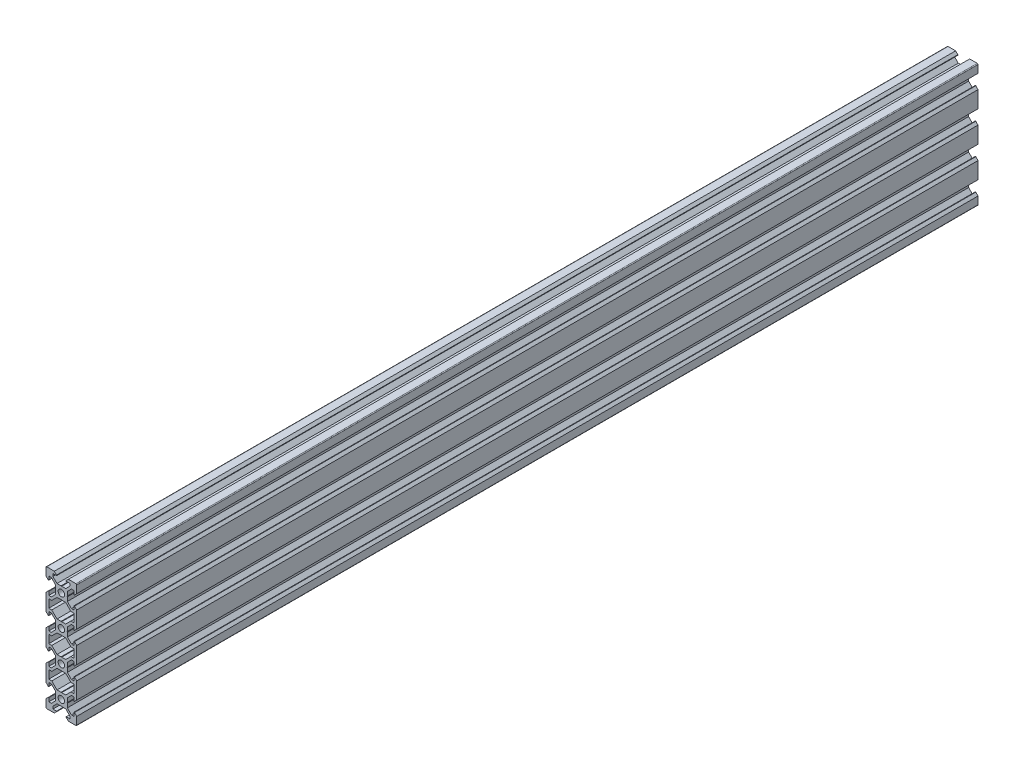
SolidWorks part; units mm, degrees
ref_plane "Plan de face" through (0, 0, 0) normal (0, 0, 1) x (1, 0, 0)
ref_plane "Plan de dessus" through (0, 0, 0) normal (0, 1, 0) x (1, 0, 0)
ref_plane "Plan de droite" through (0, 0, 0) normal (1, 0, 0) x (0, 0, -1)
ref_axis "Axe" through (0, 0, -13.782) along (0, 0, 1)
sketch "Esquisse1" plane through (0, 0, 0) normal (0, 0, 1) x (1, 0, 0)
  line L0 (0, 27.6392) -> (0, -27.6392) construction
  line L1 (-33.6074, 0) -> (33.6074, 0) construction
  line L2 (0, 0) -> (-22.2114, 22.2114) construction
  line L3 (-9.5, 10) -> (-4.58, 10)
  line L4 (-4.58, 10) -> (-3.125, 8.545)
  line L5 (-3.125, 8.545) -> (-3.125, 8.2)
  line L6 (-3.125, 8.2) -> (-5.5, 8.2)
  line L7 (-2.8393, 3.9) -> (-5.5, 6.5607)
  line L8 (-2.8393, 3.9) -> (-0.21, 3.9)
  line L9 (-5.5, 6.5607) -> (-5.5, 8.2)
  line L10 (0, 3.69) -> (0, 2.1)
  line L11 (-3.9, 2.8393) -> (-6.5607, 5.5)
  line L12 (-8.545, 3.125) -> (-8.2, 3.125)
  line L13 (-8.2, 3.125) -> (-8.2, 5.5)
  line L14 (-6.5607, 5.5) -> (-8.2, 5.5)
  line L15 (-10, 4.58) -> (-8.545, 3.125)
  line L16 (-10, 9.5) -> (-10, 4.58)
  line L17 (-0.21, 3.9) -> (0, 3.69)
  line L18 (-3.9, 2.8393) -> (-3.9, 0.21)
  line L19 (-6.2393, -12.7) -> (-8.2, -12.7)
  line L20 (-3.9, 0.21) -> (-3.69, 0)
  line L21 (-0.21, -3.9) -> (0, -3.69)
  line L22 (0, -3.69) -> (0, -2.1)
  line L23 (-6.5607, -5.5) -> (-8.2, -5.5)
  line L24 (-2.8393, -3.9) -> (-0.21, -3.9)
  line L25 (-8.545, -3.125) -> (-8.2, -3.125)
  line L26 (-10, -4.58) -> (-8.545, -3.125)
  line L27 (-8.2, -3.125) -> (-8.2, -5.5)
  line L28 (-2.8393, -3.9) -> (-6.2393, -7.3)
  line L29 (-3.9, -2.8393) -> (-6.5607, -5.5)
  line L30 (-3.9, -2.8393) -> (-3.9, -0.21)
  line L31 (-3.9, -0.21) -> (-3.69, 0)
  line L32 (-6.2393, -7.3) -> (-8.2, -7.3)
  line L33 (-8.2, -7.3) -> (-8.2, -12.7)
  line L34 (-8.2, -10) -> (-10, -10) construction
  line L35 (-10, -15.42) -> (-10, -4.58)
  line L36 (-3.9, -19.79) -> (-3.69, -20)
  line L37 (-3.9, -17.1607) -> (-3.9, -19.79)
  line L38 (-3.9, -17.1607) -> (-6.5607, -14.5)
  line L39 (-2.8393, -16.1) -> (-6.2393, -12.7)
  line L40 (-8.2, -16.875) -> (-8.2, -14.5)
  line L41 (-10, -15.42) -> (-8.545, -16.875)
  line L42 (-8.545, -16.875) -> (-8.2, -16.875)
  line L43 (-2.8393, -16.1) -> (-0.21, -16.1)
  line L44 (-6.5607, -14.5) -> (-8.2, -14.5)
  line L45 (0, -16.31) -> (0, -17.9)
  line L46 (-0.21, -16.1) -> (0, -16.31)
  line L47 (-8.2, -30) -> (-10, -30) construction
  line L48 (-3.69, -20) -> (0, -20) construction
  line L49 (-0.21, -23.9) -> (0, -23.69)
  line L50 (0, -23.69) -> (0, -22.1)
  line L51 (-6.5607, -25.5) -> (-8.2, -25.5)
  line L52 (-2.8393, -23.9) -> (-0.21, -23.9)
  line L53 (-8.545, -23.125) -> (-8.2, -23.125)
  line L54 (-10, -24.58) -> (-8.545, -23.125)
  line L55 (-8.2, -23.125) -> (-8.2, -25.5)
  line L56 (-2.8393, -23.9) -> (-6.2393, -27.3)
  line L57 (-3.9, -22.8393) -> (-6.5607, -25.5)
  line L58 (-3.9, -22.8393) -> (-3.9, -20.21)
  line L59 (-3.9, -20.21) -> (-3.69, -20)
  line L60 (-10, -24.58) -> (-10, -35.42)
  line L61 (-8.2, -32.7) -> (-8.2, -27.3)
  line L62 (-3.69, -40) -> (0, -40) construction
  line L63 (-8.2, -50) -> (-10, -50) construction
  line L64 (0, -60) -> (-22.2114, -82.2114) construction
  line L65 (-33.6074, -60) -> (33.6074, -60) construction
  line L66 (0, -87.6392) -> (0, -32.3608) construction
  line L67 (-6.2393, -32.7) -> (-8.2, -32.7)
  line L68 (-3.9, -39.79) -> (-3.69, -40)
  line L69 (-3.9, -37.1607) -> (-3.9, -39.79)
  line L70 (-3.9, -37.1607) -> (-6.5607, -34.5)
  line L71 (-2.8393, -36.1) -> (-6.2393, -32.7)
  line L72 (-8.2, -36.875) -> (-8.2, -34.5)
  line L73 (-10, -35.42) -> (-8.545, -36.875)
  line L74 (-8.545, -36.875) -> (-8.2, -36.875)
  line L75 (-6.2393, -27.3) -> (-8.2, -27.3)
  line L76 (-2.8393, -36.1) -> (-0.21, -36.1)
  line L77 (-6.5607, -34.5) -> (-8.2, -34.5)
  line L78 (0, -36.31) -> (0, -37.9)
  line L79 (-0.21, -36.1) -> (0, -36.31)
  line L80 (-0.21, -43.9) -> (0, -43.69)
  line L81 (0, -43.69) -> (0, -42.1)
  line L82 (-6.5607, -45.5) -> (-8.2, -45.5)
  line L83 (-2.8393, -43.9) -> (-0.21, -43.9)
  line L84 (-8.545, -43.125) -> (-8.2, -43.125)
  line L85 (-10, -44.58) -> (-8.545, -43.125)
  line L86 (-8.2, -43.125) -> (-8.2, -45.5)
  line L87 (-2.8393, -43.9) -> (-6.2393, -47.3)
  line L88 (-3.9, -42.8393) -> (-6.5607, -45.5)
  line L89 (-3.9, -42.8393) -> (-3.9, -40.21)
  line L90 (-3.9, -40.21) -> (-3.69, -40)
  line L91 (-10, -44.58) -> (-10, -55.42)
  line L92 (-8.2, -52.7) -> (-8.2, -47.3)
  line L93 (-6.2393, -52.7) -> (-8.2, -52.7)
  line L94 (-3.9, -59.79) -> (-3.69, -60)
  line L95 (-3.9, -57.1607) -> (-3.9, -59.79)
  line L96 (-3.9, -57.1607) -> (-6.5607, -54.5)
  line L97 (-2.8393, -56.1) -> (-6.2393, -52.7)
  line L98 (-8.2, -56.875) -> (-8.2, -54.5)
  line L99 (-10, -55.42) -> (-8.545, -56.875)
  line L100 (-8.545, -56.875) -> (-8.2, -56.875)
  line L101 (-2.8393, -56.1) -> (-0.21, -56.1)
  line L102 (-6.5607, -54.5) -> (-8.2, -54.5)
  line L103 (0, -56.31) -> (0, -57.9)
  line L104 (-0.21, -56.1) -> (0, -56.31)
  line L105 (-3.9, -60.21) -> (-3.69, -60)
  line L106 (-6.2393, -47.3) -> (-8.2, -47.3)
  line L107 (-3.9, -62.8393) -> (-3.9, -60.21)
  line L108 (-0.21, -63.9) -> (0, -63.69)
  line L109 (-10, -69.5) -> (-10, -64.58)
  line L110 (-10, -64.58) -> (-8.545, -63.125)
  line L111 (-6.5607, -65.5) -> (-8.2, -65.5)
  line L112 (-8.2, -63.125) -> (-8.2, -65.5)
  line L113 (-8.545, -63.125) -> (-8.2, -63.125)
  line L114 (-3.9, -62.8393) -> (-6.5607, -65.5)
  line L115 (0, -63.69) -> (0, -62.1)
  line L116 (-5.5, -66.5607) -> (-5.5, -68.2)
  line L117 (-2.8393, -63.9) -> (-0.21, -63.9)
  line L118 (-2.8393, -63.9) -> (-5.5, -66.5607)
  line L119 (-3.125, -68.2) -> (-5.5, -68.2)
  line L120 (-3.125, -68.545) -> (-3.125, -68.2)
  line L121 (-4.58, -70) -> (-3.125, -68.545)
  line L122 (-9.5, -70) -> (-4.58, -70)
  arc A0 (0, -2.1) -> (0, 2.1) centre (0, 0) cw
  arc A1 (-9.5, 10) -> (-10, 9.5) centre (-9.5, 9.5) ccw
  arc A2 (0, -42.1) -> (0, -37.9) centre (0, -40) cw
  arc A3 (-9.5, -70) -> (-10, -69.5) centre (-9.5, -69.5) cw
  arc A4 (0, -17.9) -> (0, -22.1) centre (0, -20) ccw
  arc A5 (0, -57.9) -> (0, -62.1) centre (0, -60) ccw
  point P4 (0, 0)
  point P7 (0, 0)
  point P30 (-10, 10)
  point P60 (0, -20)
  point P146 (-10, -70)
  dimension "D5" = 11
  dimension "D2" = 2.1
  dimension "D3" = 6.25
  dimension "D10" = 0.5
  dimension "D4" = 9.16
  dimension "D6" = 1.5
  dimension "D7" = 1.8
  dimension "D8" = 4.3
  dimension "D9" = 20
  dimension "D11" = 0.42
  dimension "D12" = 10
  dimension "D13" = 1.8
extrude "Boss.-Extru.1" add sketch "Esquisse1" along normal blind 586.8
sketch "Esquisse3" plane through (0, 0, 586.8) normal (0, 0, 1) x (1, 0, 0)
  line L0 (0, 0) -> (-9.8536, 9.8536) construction
  line L1 (-8.2, 8.2) -> (-8.2, 6.57)
  line L2 (-8.2, 6.57) -> (-7.54, 6.57)
  line L3 (-7.54, 6.57) -> (-6.57, 7.54)
  line L4 (-8.2, 3.125) -> (-8.2, 5.5) construction
  line L5 (-6.57, 8.2) -> (-6.57, 7.54)
  line L6 (-8.2, 8.2) -> (-6.57, 8.2)
  line L7 (-5.5, 6.5607) -> (-5.5, 8.2) construction
  line L8 (-10, -30) -> (6.918, -30) construction
  line L9 (-10, -24.58) -> (-10, -35.42) construction
  line L10 (-8.2, -68.2) -> (-6.57, -68.2)
  line L11 (-6.57, -68.2) -> (-6.57, -67.54)
  line L12 (-7.54, -66.57) -> (-6.57, -67.54)
  line L13 (-8.2, -66.57) -> (-7.54, -66.57)
  line L14 (-8.2, -68.2) -> (-8.2, -66.57)
  arc A0 (-9.5, 10) -> (-10, 9.5) centre (-9.5, 9.5) ccw construction
  point P13 (-7.055, 7.055)
  point P14 (-6.57, 7.87)
  point P26 (-7.055, -67.055)
  dimension "D1" = 1.07
extrude "Enlèv. mat.-Extru.1" [suppressed] cut sketch "Esquisse3" against normal through all
mirror "Symétrie1" about plane through (0, 3.69, 586.8) normal (-1, 0, 0) of "Enlèv. mat.-Extru.1", "Boss.-Extru.1"
